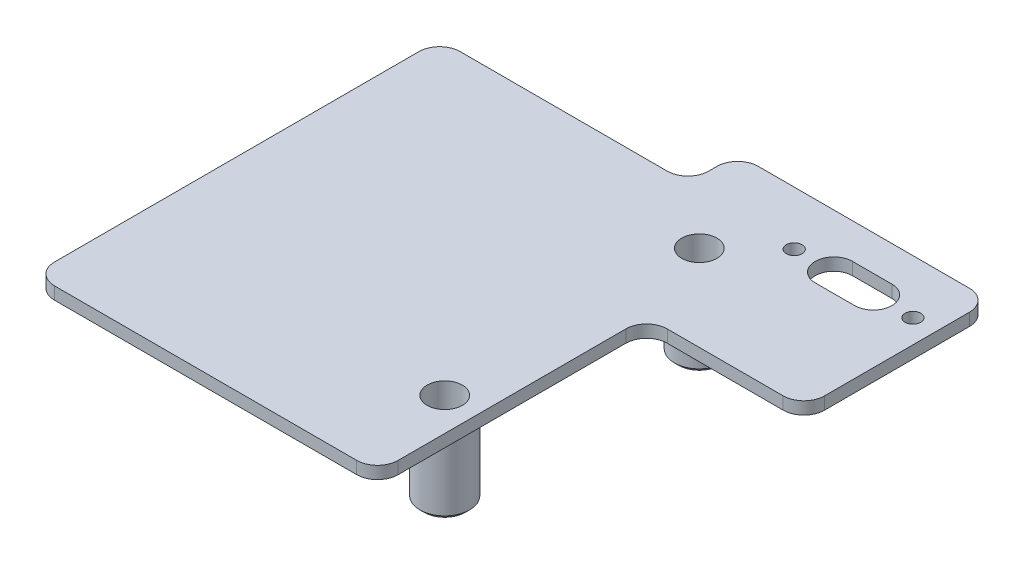
SolidWorks part; units mm, degrees
ref_plane "Front Plane" through (0, 0, 0) normal (0, 0, 1) x (1, 0, 0)
ref_plane "Top Plane" through (0, 0, 0) normal (0, 1, 0) x (1, 0, 0)
ref_plane "Right Plane" through (0, 0, 0) normal (1, 0, 0) x (0, 0, -1)
sketch "Sketch1" plane through (0, 0, 0) normal (0, 1, 0) x (1, 0, 0)
  line L0 (0, 0) -> (83, 0)
  line L1 (83, 0) -> (83, 65)
  line L2 (83, 65) -> (121, 65)
  line L3 (121, 65) -> (121, 110)
  line L4 (121, 110) -> (0, 110)
  line L5 (0, 110) -> (0, 0)
  line L6 (0, 55) -> (121, 55) construction
  line L7 (75, 85.75) -> (75, 24.25) construction
  point P11 (75, 55)
  point P13 (75, 85.75)
  point P14 (75, 24.25)
  dimension "D1" = 121
  dimension "D2" = 110
  dimension "D3" = 38
  dimension "D4" = 65
  dimension "D5" = 61.5
  dimension "D6" = 8
extrude "plate" add sketch "Sketch1" along normal blind 3
sketch "Sketch2" plane through (0, 3, 0) normal (0, 1, 0) x (1, 0, 0)
  circle A0 centre (75, 85.75) radius 6
  circle A1 centre (75, 24.25) radius 6
  dimension "D1" = 12
extrude "mount posts" add sketch "Sketch2" against normal blind 22
sketch "Sketch3" plane through (0, 3, 0) normal (0, 1, 0) x (1, 0, 0)
  circle A0 centre (75, 85.75) radius 4.25
  circle A1 centre (75, 24.25) radius 4.25
  dimension "D1" = 8.5
extrude "mount cbore" cut sketch "Sketch3" against normal blind 19.5
hole_wizard "#8 Clearance Hole1" positions "Sketch4" profile "Sketch5" hole size "#8" standard "ANSI Inch" end condition through all
sketch "Sketch4" plane through (0, -16.5, 0) normal (0, 1, 0) x (1, 0, 0)
  circle A0 centre (75, 24.25) radius 4.25 construction
  circle A1 centre (75, 85.75) radius 4.25 construction
  point P0 (75, 85.75)
  point P2 (75, 24.25)
sketch "Sketch5" plane through (75, -16.5, -85.75) normal (1, 0, 0) x (0, 0, 1)
  line L0 (0, 0) -> (0, 2.5)
  line L1 (0, 2.5) -> (2.2479, 2.5)
  line L2 (2.2479, 2.5) -> (2.2479, 0)
  line L5 (2.2479, 0) -> (0, 0)
  line L11 (0, -6.35) -> (0, 107.95) construction
  dimension "Thru Hole Dia." = 4.4958
  dimension "Thru Hole Depth" = 2.5
ref_plane "mid plane" through (0, 0, -55) normal (0, 0, -1) x (1, 0, 0)
sketch "Sketch8" plane through (0, 0, -55) normal (0, 0, -1) x (1, 0, 0)
  line L0 (47.25, 0) -> (48.85, 0)
  line L1 (0, 0) -> (121, 0) construction
  line L2 (47.25, 0) -> (45.5, 25)
  line L3 (45.5, 25) -> (47.1, 25)
  line L4 (47.1, 25) -> (48.85, 0)
  line L5 (42, 0) -> (42, 41.9178) construction
  point P9 (46.3, 25)
  dimension "D1" = 1.6
  dimension "D2" = 3.5
  dimension "D3" = 25
  dimension "D4" = 5.25
  dimension "D5" = 42
revolve "foot" add sketch "Sketch8" angle 360 about L5
fillet "Fillet1" radius 1.5 2 edges at (42, 0, -49.75) (42, 0, -48.15)
sketch "Sketch7" plane through (0, 3, 0) normal (0, 1, 0) x (1, 0, 0)
  line L0 (91.7375, 97) -> (110.2625, 97) construction
  line L1 (121, 65) -> (121, 110) construction
  line L3 (101, 88.5) -> (101, 105.5) construction
  line L4 (96.2375, 101.5) -> (105.7625, 101.5)
  line L5 (81, 105.5) -> (121, 105.5) construction
  line L6 (81, 105.5) -> (81, 88.5) construction
  line L7 (81, 88.5) -> (121, 88.5) construction
  line L8 (121, 105.5) -> (121, 88.5) construction
  line L9 (81, 105.5) -> (121, 88.5) construction
  line L10 (81, 88.5) -> (121, 105.5) construction
  line L11 (96.2375, 92.5) -> (105.7625, 92.5)
  line L13 (121, 110) -> (0, 110) construction
  circle A0 centre (96.2375, 97) radius 4.5 construction
  circle A1 centre (105.7625, 97) radius 4.5 construction
  arc A2 (96.2375, 101.5) -> (96.2375, 92.5) centre (96.2375, 97) ccw
  arc A3 (105.7625, 101.5) -> (105.7625, 92.5) centre (105.7625, 97) cw
  circle A4 centre (115.34, 97) radius 1.9
  circle A5 centre (86.66, 97) radius 1.9
  point P16 (101, 97)
  dimension "D2" = 9.525
  dimension "D5" = 9
  dimension "D6" = 3.8
  dimension "D1" = 13
  dimension "D3" = 40
  dimension "D4" = 17
  dimension "D7" = 28.68
extrude "terminal strip" cut sketch "Sketch7" against normal through all
sketch "Sketch9" plane through (0, 3, 0) normal (0, 1, 0) x (1, 0, 0)
  line L0 (0, 98) -> (60, 98)
  line L1 (0, 110) -> (0, 0) construction
  line L2 (60, 98) -> (60, 110)
  line L3 (121, 110) -> (0, 110) construction
  line L4 (60, 110) -> (0, 110)
  line L5 (0, 110) -> (0, 98)
  dimension "D1" = 60
  dimension "D2" = 12
extrude "wiring relief" cut sketch "Sketch9" against normal through all
chamfer "Chamfer1" distance 3 angle 45 2 edges at (75, -16.5, -81.5) (75, -16.5, -20)
chamfer "Chamfer2" distance 1 angle 45 2 edges at (75, -19, -18.25) (75, -19, -79.75)
fillet "Fillet2" radius 5 8 edges at (121, 1.5, -110) (121, 1.5, -65) (83, 1.5, -65) (83, 1.5, 0) (0, 1.5, 0) (60, 1.5, -110) (60, 1.5, -98) (0, 1.5, -98)
fillet "Fillet3" radius 1.5 2 edges at (75, 0, -79.75) (75, 0, -18.25)
